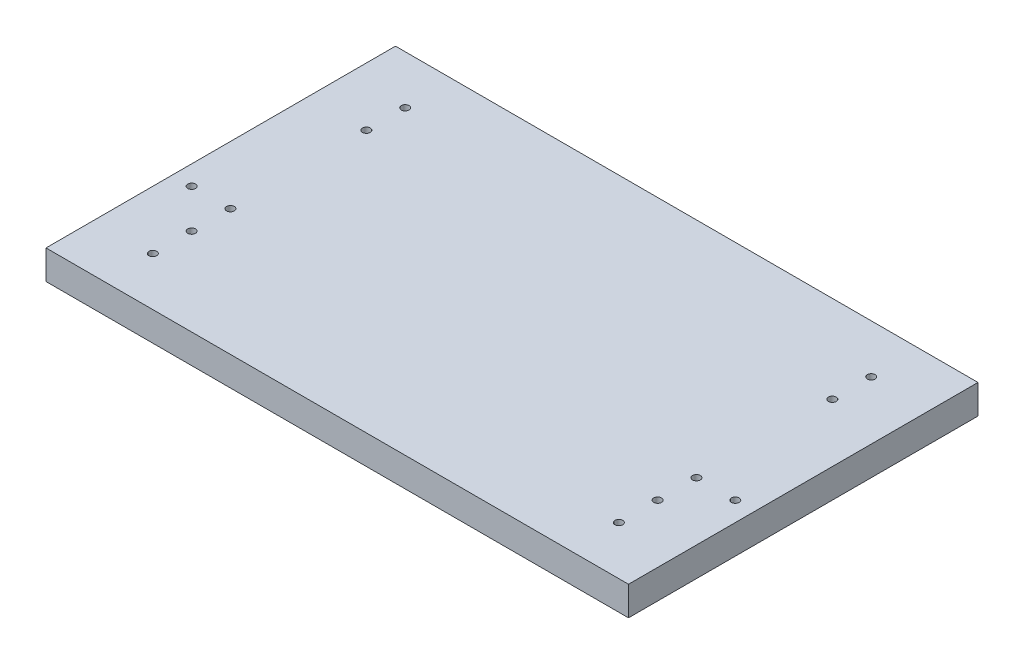
SolidWorks part; units mm, degrees
ref_plane "Alzado" through (0, 0, 0) normal (0, 0, 1) x (1, 0, 0)
ref_plane "Planta" through (0, 0, 0) normal (0, 1, 0) x (1, 0, 0)
ref_plane "Vista lateral" through (0, 0, 0) normal (1, 0, 0) x (0, 0, -1)
sketch "Croquis1" plane through (0, 0, 0) normal (0, 1, 0) x (1, 0, 0)
  line L1 (-150, -90) -> (150, -90)
  line L2 (-150, -90) -> (-150, 90)
  line L3 (-150, 90) -> (150, 90)
  line L4 (150, -90) -> (150, 90)
  line L5 (-150, -90) -> (150, 90) construction
  line L6 (-150, 90) -> (150, -90) construction
  point P0 (0, 0)
  dimension "D1" = 300
  dimension "D2" = 180
extrude "Saliente-Extruir1" add sketch "Croquis1" along normal blind 15
sketch "Croquis2" plane through (0, 15, 0) normal (0, 1, 0) x (1, 0, 0)
  line L0 (150, 90) -> (-150, 90) construction
  line L1 (-150, -90) -> (150, -90) construction
  line L2 (-150, 90) -> (-150, -90) construction
  line L3 (150, -90) -> (150, 90) construction
  circle A0 centre (-120, -65) radius 2
  circle A1 centre (-120, -45) radius 2
  circle A2 centre (120, -65) radius 2
  circle A3 centre (120, -45) radius 2
  circle A4 centre (-140, -25) radius 2
  circle A5 centre (-120, -25) radius 2
  circle A6 centre (120, -25) radius 2
  circle A7 centre (140, -25) radius 2
  circle A8 centre (-120, 65) radius 2
  circle A9 centre (-120, 45) radius 2
  circle A10 centre (120, 45) radius 2
  circle A11 centre (120, 65) radius 2
  dimension "D1" = 25
  dimension "D2" = 0
  dimension "D3" = 25
  dimension "D4" = 0
  dimension "D7" = 10
  dimension "D8" = 20
  dimension "D9" = 30
  dimension "D10" = 10
  dimension "D15" = 25
  dimension "D19" = 45
  dimension "D5" = 30
  dimension "D6" = 30
  dimension "D11" = 65
  dimension "D12" = 0
  dimension "D13" = 65
  dimension "D14" = 0
  dimension "D16" = 20
  dimension "D17" = 25
  dimension "D18" = 20
  dimension "D20" = 45
extrude "Cortar-Extruir1" cut sketch "Croquis2" against normal blind 10
sketch "Croquis3" plane through (0, 0, 0) normal (0, -1, 0) x (1, 0, 0)
  line L2 (-150, -90) -> (-150, 90) construction
  line L3 (150, -90) -> (-150, -90) construction
  circle A0 centre (-140, -65) radius 2
  dimension "D1" = 10
  dimension "D2" = 25
extrude "Cortar-Extruir2" cut sketch "Croquis3" against normal blind 10
